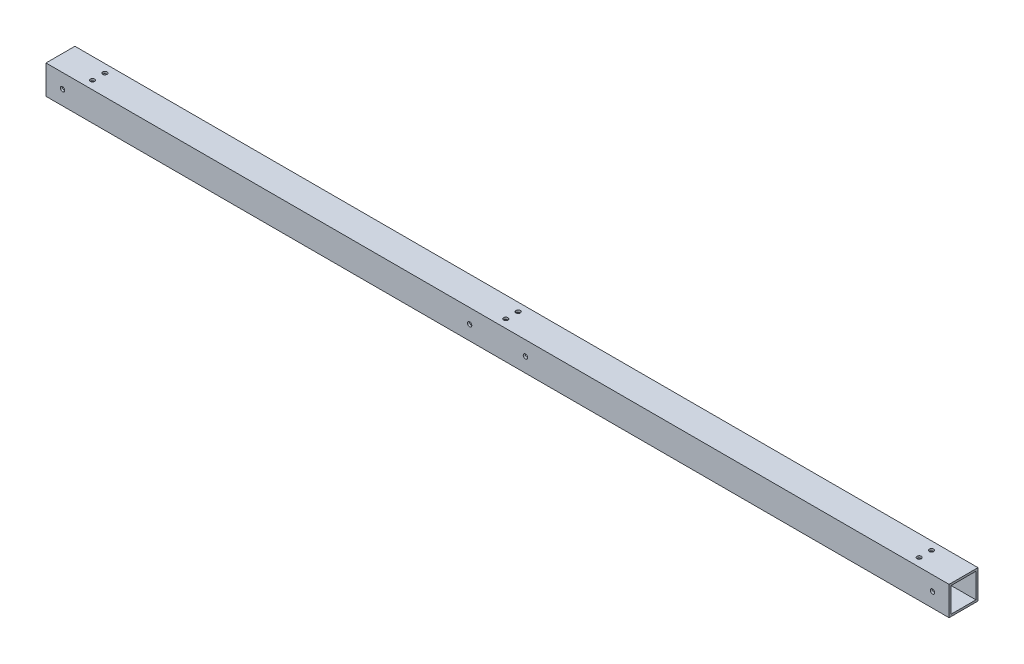
SolidWorks part; units mm, degrees
material "6061-T6 (SS)"
ref_plane "Front Plane" through (0, 0, 0) normal (0, 0, 1) x (1, 0, 0)
ref_plane "Top Plane" through (0, 0, 0) normal (0, 1, 0) x (1, 0, 0)
ref_plane "Right Plane" through (0, 0, 0) normal (1, 0, 0) x (0, 0, -1)
sketch "Sketch1" plane through (0, 0, 0) normal (1, 0, 0) x (0, 0, -1)
  line L1 (-22.225, -22.225) -> (22.225, -22.225)
  line L2 (-22.225, -22.225) -> (-22.225, 22.225)
  line L3 (-22.225, 22.225) -> (22.225, 22.225)
  line L4 (22.225, -22.225) -> (22.225, 22.225)
  line L5 (-22.225, -22.225) -> (22.225, 22.225) construction
  line L6 (-22.225, 22.225) -> (22.225, -22.225) construction
  line L7 (-19.05, -19.05) -> (19.05, -19.05)
  line L8 (-19.05, -19.05) -> (-19.05, 19.05)
  line L9 (-19.05, 19.05) -> (19.05, 19.05)
  line L10 (19.05, -19.05) -> (19.05, 19.05)
  line L11 (-19.05, -19.05) -> (19.05, 19.05) construction
  line L12 (-19.05, 19.05) -> (19.05, -19.05) construction
  point P0 (0, 0)
  point P6 (0, 0)
  dimension "D1" = 44.45
  dimension "D2" = 3.175
extrude "Boss-Extrude1" add sketch "Sketch1" along normal blind 693.7375 and the other way blind 693.7375
hole_wizard "17/64 (0.26563) Diameter Hole2" positions "Sketch4" profile "Sketch5" hole size "17/64" standard "ANSI Inch" end condition through all
sketch "Sketch4" plane through (0, 0, 22.225) normal (0, 0, 1) x (1, 0, 0)
  line L0 (-693.7375, 22.225) -> (-693.7375, -22.225) construction
  line L1 (0, 22.225) -> (0, -22.225) construction
  line L2 (-693.7375, 22.225) -> (693.7375, 22.225) construction
  line L3 (-693.7375, -22.225) -> (693.7375, -22.225) construction
  point P0 (42.8625, 0)
  point P6 (-668.3375, 0)
  point P19 (668.3375, 0)
  point P20 (-42.8625, 0)
  dimension "D1" = 25.4
  dimension "D2" = 711.2
sketch "Sketch5" plane through (42.8625, 0, 22.225) normal (1, 0, 0) x (0, -1, 0)
  line L0 (0, 0) -> (0, 44.45)
  line L1 (0, 44.45) -> (3.3735, 44.45)
  line L2 (3.3735, 44.45) -> (3.3735, 0)
  line L5 (3.3735, 0) -> (0, 0)
  line L11 (0, -6.35) -> (0, 107.95) construction
  dimension "Thru Hole Dia." = 6.747
  dimension "Thru Hole Depth" = 44.45
hole_wizard "17/64 (0.26563) Diameter Hole1" positions "Sketch6" profile "Sketch7" hole size "17/64" standard "ANSI Inch" end condition through all
sketch "Sketch6" plane through (0, -22.225, 0) normal (0, -1, 0) x (-1, 0, 0)
  line L0 (0, 9.525) -> (0, -9.525) construction
  line L2 (-635, 9.525) -> (0, 9.525) construction
  line L3 (0, 9.525) -> (635, 9.525) construction
  point P0 (0, 9.525)
  point P2 (0, -9.525)
  point P4 (-635, 9.525)
  point P6 (-635, -9.525)
  point P8 (635, -9.525)
  point P10 (635, 9.525)
  dimension "D1" = 635
  dimension "D2" = 19.05
sketch "Sketch7" plane through (0, -22.225, -9.525) normal (1, 0, 0) x (0, 0, -1)
  line L0 (0, 0) -> (0, 44.45)
  line L1 (0, 44.45) -> (3.3735, 44.45)
  line L2 (3.3735, 44.45) -> (3.3735, 0)
  line L5 (3.3735, 0) -> (0, 0)
  line L11 (0, -6.35) -> (0, 107.95) construction
  dimension "Thru Hole Dia." = 6.747
  dimension "Thru Hole Depth" = 44.45
